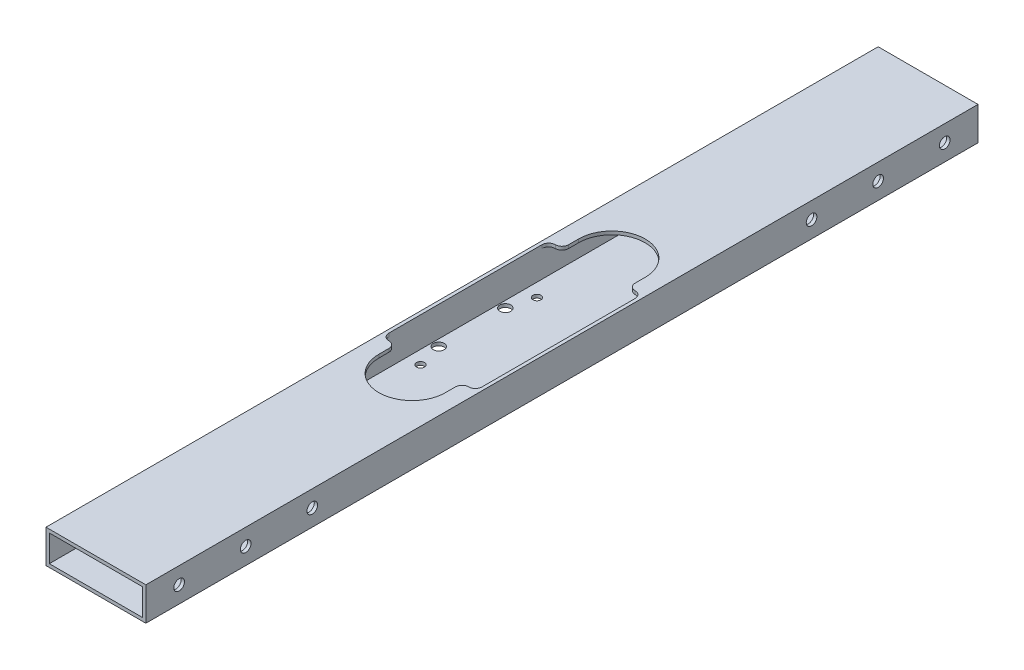
SolidWorks part; units mm, degrees
material "6061 合金"
ref_plane "前视基准面" through (0, 0, 0) normal (0, 0, 1) x (1, 0, 0)
ref_plane "上视基准面" through (0, 0, 0) normal (0, 1, 0) x (1, 0, 0)
ref_plane "右视基准面" through (0, 0, 0) normal (1, 0, 0) x (0, 0, -1)
other "Configuration Table"
sketch "草图1" plane through (0, 0, 0) normal (0, 0, 1) x (1, 0, 0)
  line L1 (-15, 5) -> (15, 5)
  line L2 (-15, 5) -> (-15, -5)
  line L3 (-15, -5) -> (15, -5)
  line L4 (15, 5) -> (15, -5)
  line L5 (-15, 5) -> (15, -5) construction
  line L6 (-15, -5) -> (15, 5) construction
  line L7 (-13.5, 3.5) -> (13.5, 3.5)
  line L8 (-13.5, 3.5) -> (-13.5, -3.5)
  line L9 (-13.5, -3.5) -> (13.5, -3.5)
  line L10 (13.5, 3.5) -> (13.5, -3.5)
  line L11 (-13.5, 3.5) -> (13.5, -3.5) construction
  line L12 (-13.5, -3.5) -> (13.5, 3.5) construction
  point P0 (0, 0)
  point P6 (0, 0)
  dimension "D1" = 1.5
  dimension "D2" = 1.5
  dimension "D3" = 10
  dimension "D4" = 30
extrude "凸台-拉伸1" add sketch "草图1" along normal blind 250
sketch "草图2" plane through (15, 0, 0) normal (1, 0, 0) x (0, 0, -1)
  line L0 (0, 0) -> (-281.3553, 0) construction
  line L1 (-250, -5) -> (-250, 5) construction
  line L2 (-240, 0) -> (-220, 0) construction
  line L3 (-125, 5) -> (-125, 97.1982) construction
  line L4 (-250, 5) -> (0, 5) construction
  circle A0 centre (-240, 0) radius 1.6
  circle A1 centre (-220, 0) radius 1.6
  circle A2 centre (-200, 0) radius 1.6
  circle A3 centre (-50, 0) radius 1.6
  circle A4 centre (-30, 0) radius 1.6
  circle A5 centre (-10, 0) radius 1.6
  dimension "D1" = 10
  dimension "D2" = 3.2
  dimension "D4" = 20
  dimension "D3" = 3
extrude "切除-拉伸1" cut sketch "草图2" against normal through all
sketch "草图5" plane through (0, 5, 0) normal (0, 1, 0) x (1, 0, 0)
  line L0 (0, -15) -> (0, -65) construction
  line L1 (9, -15) -> (9, -65)
  line L2 (-9, -15) -> (-9, -65)
  line L3 (15, -250) -> (15, 0) construction
  line L4 (15, -125) -> (-58.6377, -125) construction
  line L5 (0, -235) -> (0, -185) construction
  line L6 (9, -235) -> (9, -185)
  line L7 (-9, -235) -> (-9, -185)
  arc A0 (9, -15) -> (-9, -15) centre (0, -15) ccw
  arc A1 (-9, -65) -> (9, -65) centre (0, -65) ccw
  arc A2 (9, -235) -> (-9, -235) centre (0, -235) cw
  arc A3 (-9, -185) -> (9, -185) centre (0, -185) cw
  point P2 (0, -40)
  point P14 (0, -210)
  dimension "D1" = 6
  dimension "D2" = 15
  dimension "D3" = 50
extrude "切除-拉伸4" [suppressed] cut sketch "草图5" against normal through all
sketch "草图6" plane through (0, 0, 0) normal (0, 0, -1) x (-1, 0, 0)
  line L0 (-13.5, 3.5) -> (13.5, 3.5) construction
  line L1 (-14, 4) -> (14, 4)
  line L2 (-14, 4) -> (-14, -4)
  line L3 (-14, -4) -> (14, -4)
  line L4 (14, 4) -> (14, -4)
  line L5 (13.5, 3.5) -> (13.5, -3.5) construction
  line L6 (13.5, -3.5) -> (-13.5, -3.5) construction
  line L7 (-13.5, -3.5) -> (-13.5, 3.5) construction
  dimension "D1" = 0.5
  dimension "D2" = 0.5
  dimension "D3" = 0.5
  dimension "D4" = 0.5
extrude "切除-拉伸5" cut sketch "草图6" against normal blind 330
sketch "草图8" plane through (0, 5, 0) normal (0, 1, 0) x (1, 0, 0)
  line L0 (-15, -125) -> (256.2304, -125) construction
  line L1 (-15, -250) -> (-15, 0) construction
  line L2 (0, 0) -> (0, -273.1347) construction
  line L3 (-10, -155) -> (-10, -95)
  line L5 (0, -165) -> (0, -85)
  line L7 (10, -155) -> (10, -95)
  line L8 (15, -250) -> (15, 0) construction
  line L9 (10, -125) -> (14, -125)
  line L10 (10, -125) -> (10, -100)
  line L11 (10, -100) -> (14, -100)
  line L12 (14, -150) -> (14, -100)
  line L13 (10, -150) -> (14, -150)
  line L14 (10, -100) -> (14, -100)
  line L15 (10, -150) -> (14, -150)
  line L16 (15, -125) -> (-256.2304, -125) construction
  line L17 (-10, -150) -> (-14, -150)
  line L18 (-10, -100) -> (-14, -100)
  line L19 (-10, -150) -> (-14, -150)
  line L20 (-14, -150) -> (-14, -100)
  line L21 (-10, -100) -> (-14, -100)
  line L22 (-10, -125) -> (-14, -125)
  arc A0 (-10, -95) -> (10, -95) centre (0, -95) cw
  arc A1 (-10, -155) -> (10, -155) centre (0, -155) ccw
  point P7 (-10, -125)
  point P17 (10, -125)
  point P18 (0, -125)
  dimension "D1" = 10
  dimension "D2" = 1
  dimension "D3" = 30
  dimension "D4" = 50
extrude "切除-拉伸6" cut sketch "草图8" against normal blind 5 contours L3 A1 L5 A0 | L5 A1 L7 A0 | L9 L12 L11 L7 | L7 L13 L12 L9 | L22 L3 L18 L20 | L3 L22 L20 L17 region at (-4.8432, 5, 125) region at (-12, 5, 137.5) region at (4.8432, 5, 125) region at (-12, 5, 112.5) region at (12, 5, 137.5) region at (12, 5, 112.5)
sketch "草图10" plane through (0, -5, 0) normal (0, -1, 0) x (1, 0, 0)
  line L0 (-15, 125) -> (132.4304, 125) construction
  line L1 (-15, 250) -> (-15, 0) construction
  line L3 (-64.4859, 74.5198) -> (-104.4859, 74.5198)
  line L4 (-64.4859, 74.5198) -> (-64.4859, 34.8198)
  line L5 (-64.4859, 34.8198) -> (-104.4859, 34.8198)
  line L6 (-104.4859, 74.5198) -> (-104.4859, 34.8198)
  line L7 (-64.4859, 74.5198) -> (-104.4859, 34.8198) construction
  line L8 (-64.4859, 34.8198) -> (-104.4859, 74.5198) construction
  circle A0 centre (-84.4859, 42.8198) radius 1.65
  circle A1 centre (-94.4859, 66.5198) radius 1.65
  circle A2 centre (-74.4859, 66.5198) radius 1.65
  circle A3 centre (-12, 115) radius 1.65
  circle A4 centre (-12, 135) radius 1.65
  circle A5 centre (11.7, 125) radius 1.65
  point P4 (-84.4859, 54.6698)
  dimension "D1" = 3.3
  dimension "D2" = 3.3
  dimension "D3" = 20
  dimension "D8" = 10
  dimension "D9" = 10
  dimension "D10" = 8
  dimension "D12" = 3.3
  dimension "D13" = 20
  dimension "D14" = 3.3
  dimension "D15" = 23.7
  dimension "D16" = 3
  dimension "D4" = 23.7
  dimension "D5" = 8
  dimension "D6" = 8
  dimension "D7" = 40
  dimension "D11" = 39.7
extrude "切除-拉伸7" cut sketch "草图10" against normal blind 25
fillet "圆角1" radius 2 8 edges at (10, 4.5, 100) (-10, 4.5, 100) (-14, 4.5, 150) (-10, 4.5, 150) (10, 4.5, 150) (14, 4.5, 150) (14, 4.5, 100) (-14, 4.5, 100)
sketch "草图11" plane through (0, -5, 0) normal (0, -1, 0) x (1, 0, 0)
  line L0 (-15, 125) -> (77.8938, 125) construction
  line L1 (-15, 250) -> (-15, 0) construction
  line L2 (0, 250) -> (0, -21.6226) construction
  line L3 (-15, 250) -> (15, 250) construction
  line L4 (0, 0) -> (0, 271.6226) construction
  circle A0 centre (-10, 142.5) radius 1.2
  circle A1 centre (10, 142.5) radius 1.2
  circle A2 centre (10, 107.5) radius 1.2
  circle A3 centre (-10, 107.5) radius 1.2
  dimension "D1" = 2.4
  dimension "D2" = 20
  dimension "D3" = 35
extrude "切除-拉伸8" cut sketch "草图11" against normal blind 25
